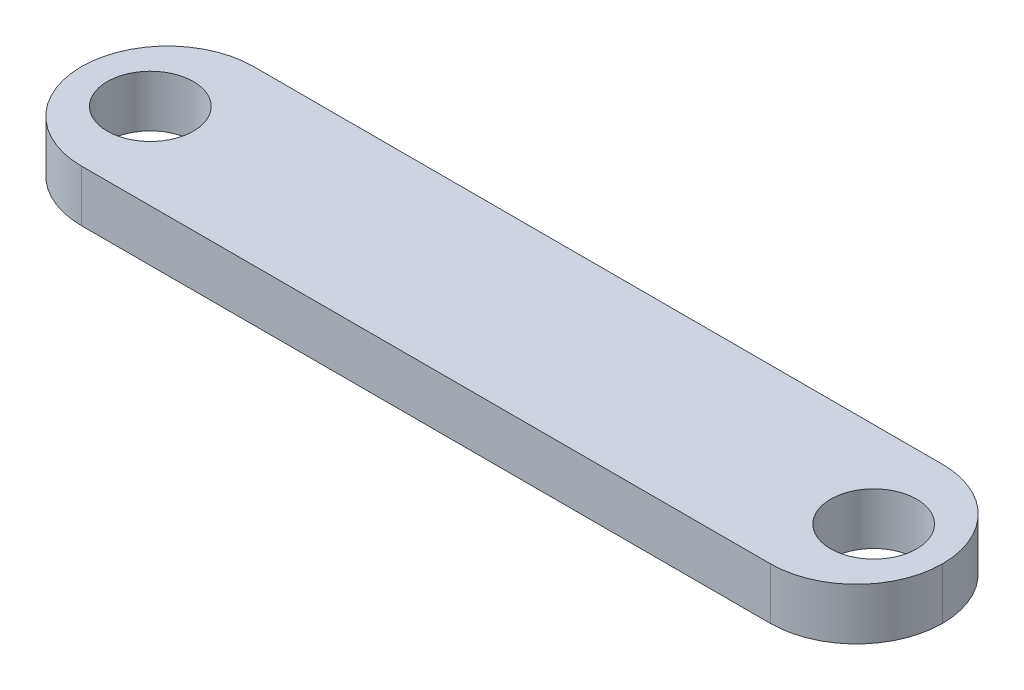
SolidWorks part; units mm, degrees
ref_plane "Front Plane" through (0, 0, 0) normal (0, 0, 1) x (1, 0, 0)
ref_plane "Top Plane" through (0, 0, 0) normal (0, 1, 0) x (1, 0, 0)
ref_plane "Right Plane" through (0, 0, 0) normal (1, 0, 0) x (0, 0, -1)
sketch "Sketch1" plane through (0, 0, 0) normal (0, 1, 0) x (1, 0, 0)
  line L1 (0, 0) -> (100, 0)
  line L2 (0, 0) -> (0, 20)
  line L3 (0, 20) -> (100, 20)
  line L4 (100, 0) -> (100, 20)
  dimension "D1" = 100
  dimension "D2" = 20
extrude "Boss-Extrude1" add sketch "Sketch1" along normal blind 6
sketch "Sketch2" plane through (0, 6, 0) normal (0, 1, 0) x (1, 0, 0)
  line L0 (100, 20) -> (0, 20) construction
  line L1 (0, 20) -> (0, 0) construction
  circle A0 centre (8, 10) radius 5
  dimension "D1" = 10
  dimension "D2" = 8
extrude "Cut-Extrude1" cut sketch "Sketch2" against normal blind 6
fillet "Fillet1" radius 10 4 edges at (100, 3, 0) (100, 3, -20) (0, 3, 0) (0, 3, -20)
sketch "Sketch3" plane through (0, 6, 0) normal (0, 1, 0) x (1, 0, 0)
  line L0 (90, 20) -> (10, 20) construction
  circle A0 centre (92, 10) radius 5
  dimension "D1" = 8
  dimension "D2" = 10
extrude "Cut-Extrude2" cut sketch "Sketch3" against normal through all
